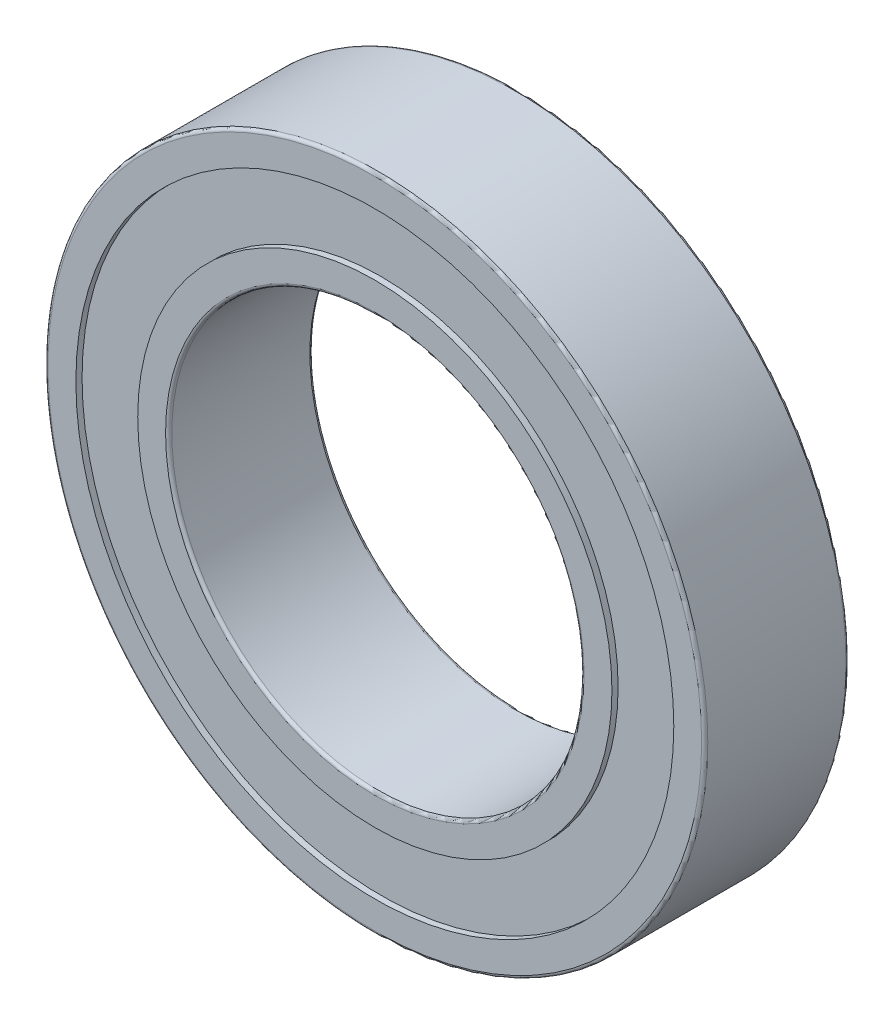
SolidWorks part; units mm, degrees
ref_plane "Front Plane" through (0, 0, 0) normal (0, 0, 1) x (1, 0, 0)
ref_plane "Top Plane" through (0, 0, 0) normal (0, 1, 0) x (1, 0, 0)
ref_plane "Right Plane" through (0, 0, 0) normal (1, 0, 0) x (0, 0, -1)
sketch "Sketch1" plane through (0, 0, 0) normal (0, 0, 1) x (1, 0, 0)
  circle A0 centre (0, 0) radius 10
  circle A1 centre (0, 0) radius 16
  dimension "D1" = 20
  dimension "D2" = 32
extrude "Boss-Extrude1" add sketch "Sketch1" along normal blind 7
sketch "Sketch2" plane through (0, 0, 7) normal (0, 0, 1) x (1, 0, 0)
  circle A2 centre (0, 0) radius 14.5
  circle A3 centre (0, 0) radius 14.5
  circle A5 centre (0, 0) radius 11.5
  circle A6 centre (0, 0) radius 11.5
  dimension "D1" = 1.5
  dimension "D2" = 1.5
extrude "Cut-Extrude1" cut sketch "Sketch2" against normal blind 0.3
extrude "Cut-Extrude2" cut sketch "Sketch2<2>" along normal blind 0.5 from surface starting at face at (16, 0, 0)
sketch "Sketch2<2>" plane through (0, 0, 7) normal (0, 0, 1) x (1, 0, 0) same geometry as "Sketch2"
fillet "Fillet1" radius 0.15 4 edges at (10, 0, 7) (16, 0, 7) (10, 0, 0) (16, 0, 0)
